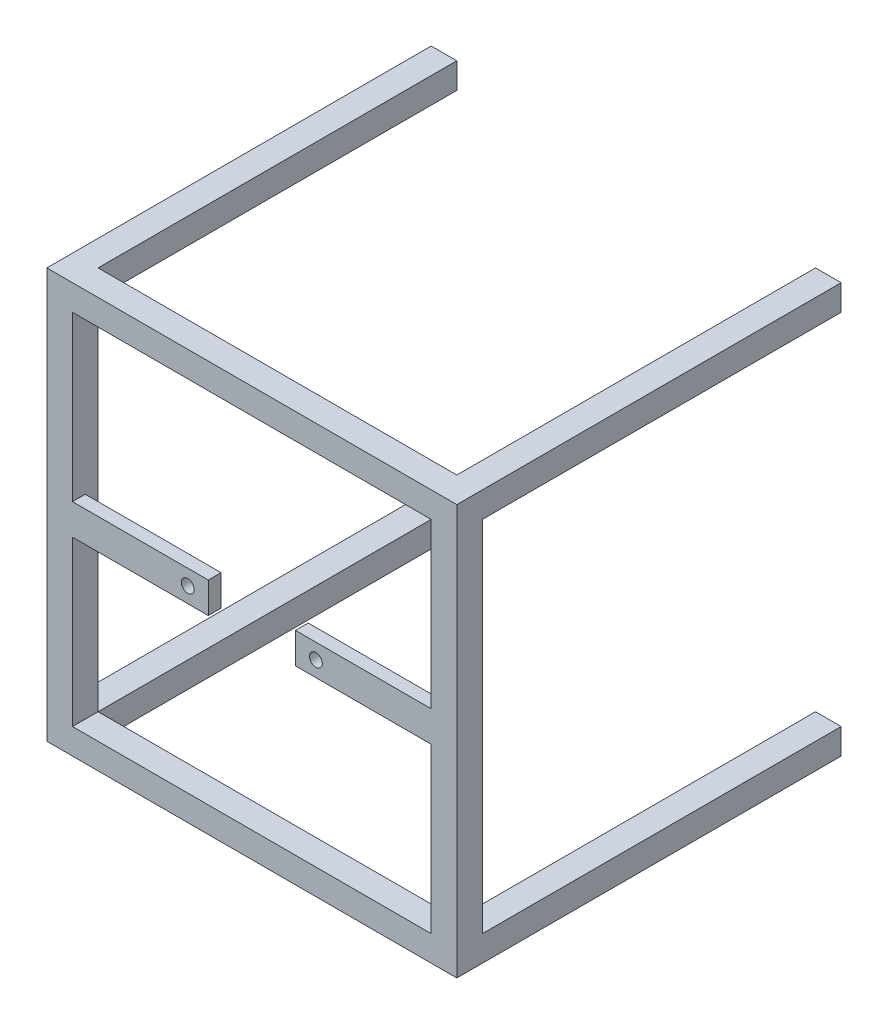
SolidWorks part; units mm, degrees
ref_plane "Alzado" through (0, 0, 0) normal (0, 0, 1) x (1, 0, 0)
ref_plane "Planta" through (0, 0, 0) normal (0, 1, 0) x (1, 0, 0)
ref_plane "Vista lateral" through (0, 0, 0) normal (1, 0, 0) x (0, 0, -1)
sketch "Croquis1" plane through (0, 0, 0) normal (0, 0, 1) x (1, 0, 0)
  line L0 (5, -10) -> (5, 0) construction
  line L1 (0, 0) -> (10, 0)
  line L2 (0, 0) -> (0, -10)
  line L3 (0, -10) -> (10, -10)
  line L4 (10, 0) -> (10, -10)
  line L6 (10, -5) -> (0, -5) construction
  line L7 (4, -10) -> (6, -10)
  line L8 (4, -10) -> (4, -8)
  line L9 (4, -8) -> (6, -8)
  line L10 (6, -10) -> (6, -8)
  line L11 (10, 0) -> (210, 0)
  line L12 (10, 0) -> (10, -10)
  line L13 (10, -10) -> (210, -10)
  line L14 (210, 0) -> (210, -10)
  dimension "D1" = 10
  dimension "D2" = 10
  dimension "D3" = 2
  dimension "D4" = 1
  dimension "D5" = 2
  dimension "D6" = 200
sketch "Croquis2" plane through (0, 0, 0) normal (0, 0, 1) x (1, 0, 0)
  line L0 (10, -10) -> (10, -150)
  line L1 (0, 0) -> (160, 0)
  line L2 (0, 0) -> (0, -160)
  line L3 (0, -160) -> (160, -160)
  line L4 (160, 0) -> (160, -160)
  line L5 (10, -150) -> (150, -150)
  line L6 (150, -10) -> (150, -150)
  line L7 (10, -10) -> (150, -10)
  dimension "D1" = 160
  dimension "D2" = 160
  dimension "D3" = 10
extrude "Saliente-Extruir1" add sketch "Croquis2" along normal blind 10
sketch "Croquis3" plane through (0, 0, 10) normal (0, 0, 1) x (1, 0, 0)
  line L0 (0, -160) -> (10, -150) construction
  line L1 (10, -150) -> (150, -150) construction
  line L2 (160, 0) -> (150, -10) construction
  line L3 (156, -4) -> (156, -156)
  line L4 (155, -5) -> (5, -5)
  line L5 (155, -5) -> (155, -155)
  line L6 (155, -155) -> (5, -155)
  line L7 (5, -5) -> (5, -155)
  line L8 (156, -156) -> (4, -156)
  line L9 (4, -4) -> (4, -156)
  line L10 (156, -4) -> (4, -4)
  line L11 (154, -6) -> (154, -154)
  line L12 (154, -154) -> (6, -154)
  line L13 (6, -6) -> (6, -154)
  line L14 (154, -6) -> (6, -6)
  dimension "D1" = 1
  dimension "D2" = 1
extrude "Cortar-Extruir1" cut sketch "Croquis3" against normal blind 3.5 contours L3 L10 L9 L8 L7 L4 L5 L6 | L4 L7 L6 L5 L14 L11 L12 L13 region at (155.785, -80, 10) region at (154.7879, -80, 10)
sketch "Croquis4" plane through (0, 0, 10) normal (0, 0, 1) x (1, 0, 0)
  line L1 (0, 0) -> (10, 0)
  line L2 (0, 0) -> (0, -10)
  line L3 (0, -10) -> (10, -10)
  line L4 (10, 0) -> (10, -10)
  line L5 (160, 0) -> (150, 0)
  line L6 (160, 0) -> (160, -10)
  line L7 (160, -10) -> (150, -10)
  line L8 (150, 0) -> (150, -10)
  line L9 (150, -150) -> (160, -150)
  line L10 (150, -150) -> (150, -160)
  line L11 (150, -160) -> (160, -160)
  line L12 (160, -150) -> (160, -160)
  line L13 (10, -150) -> (0, -150)
  line L14 (10, -150) -> (10, -160)
  line L15 (10, -160) -> (0, -160)
  line L16 (0, -150) -> (0, -160)
extrude "Saliente-Extruir2" add sketch "Croquis4" along normal blind 140 and the other way blind 10
sketch "Croquis7" plane through (0, 0, 150) normal (0, 0, 1) x (1, 0, 0)
  line L1 (0, 0) -> (160, 0)
  line L2 (0, 0) -> (0, -160)
  line L3 (0, -160) -> (160, -160)
  line L4 (160, 0) -> (160, -160)
  line L5 (10, -10) -> (150, -10)
  line L6 (10, -10) -> (10, -150)
  line L7 (10, -150) -> (150, -150)
  line L8 (150, -10) -> (150, -150)
extrude "Saliente-Extruir3" add sketch "Croquis7" along normal blind 10
ref_plane "PlanoX" through (0, 0, 80) normal (0, 0, 1) x (1, 0, 0)
ref_plane "PlanoY" through (0, -80, 0) normal (0, 1, 0) x (1, 0, 0)
ref_plane "PlanoZ" through (80, 0, 0) normal (1, 0, 0) x (0, 0, -1)
ref_axis "EjeXY" through (-11, -80, 80) along (1, 0, 0)
ref_axis "EjeYZ" through (80, -80, -11) along (0, 0, 1)
ref_axis "EjeXZ" through (80, 11, 80) along (0, -1, 0)
sketch "Croquis8" plane through (0, 0, 160) normal (0, 0, 1) x (1, 0, 0)
  line L0 (0, -80) -> (160, -80) construction
  line L1 (0, 0) -> (0, -160) construction
  line L2 (160, -160) -> (160, 0) construction
  line L3 (63, -80) -> (63, -74) construction
  line L4 (80, -121) -> (80, 121) construction
  line L5 (63, -74) -> (0, -74)
  line L6 (63, -74) -> (63, -86)
  line L7 (63, -86) -> (0, -86)
  line L8 (0, -74) -> (0, -86)
  line L9 (97, -86) -> (160, -86)
  line L10 (160, -74) -> (160, -86)
  line L11 (97, -74) -> (160, -74)
  line L12 (97, -74) -> (97, -86)
  circle A0 centre (55, -80) radius 2.5
  circle A1 centre (105, -80) radius 2.5
  point P8 (80, -80)
  dimension "D1" = 5
  dimension "D2" = 25
  dimension "D3" = 8
  dimension "D4" = 6
  dimension "D5" = 12
extrude "Saliente-Extruir4" add sketch "Croquis8" against normal blind 5
sketch "Croquis9" plane through (0, 0, 0) normal (-1, 0, 0) x (0, 0, 1)
  line L0 (10, -10) -> (10, -150) construction
  line L1 (0, 0) -> (10, 0)
  line L2 (0, 0) -> (0, -160)
  line L3 (0, -160) -> (10, -160)
  line L4 (10, 0) -> (10, -160)
  dimension "D1" = 160
extrude "Cortar-Extruir2" cut sketch "Croquis9" against normal through all
sketch "Croquis10" plane through (0, 0, 10) normal (0, 0, -1) x (-1, 0, 0)
  line L0 (-150, -150) -> (-160, -160) construction
  line L1 (0, -160) -> (-10, -150) construction
  line L2 (-150, -10) -> (-160, 0) construction
  line L3 (-10, -10) -> (0, 0) construction
  circle A0 centre (-155, -155) radius 2.5
  circle A1 centre (-5, -5) radius 2.5
  circle A2 centre (-155, -5) radius 2.5
  circle A3 centre (-5, -155) radius 2.5
  dimension "D1" = 5
  dimension "D2" = 5
  dimension "D3" = 5
  dimension "D4" = 5
extrude "Cortar-Extruir3" cut sketch "Croquis10" against normal blind 5
